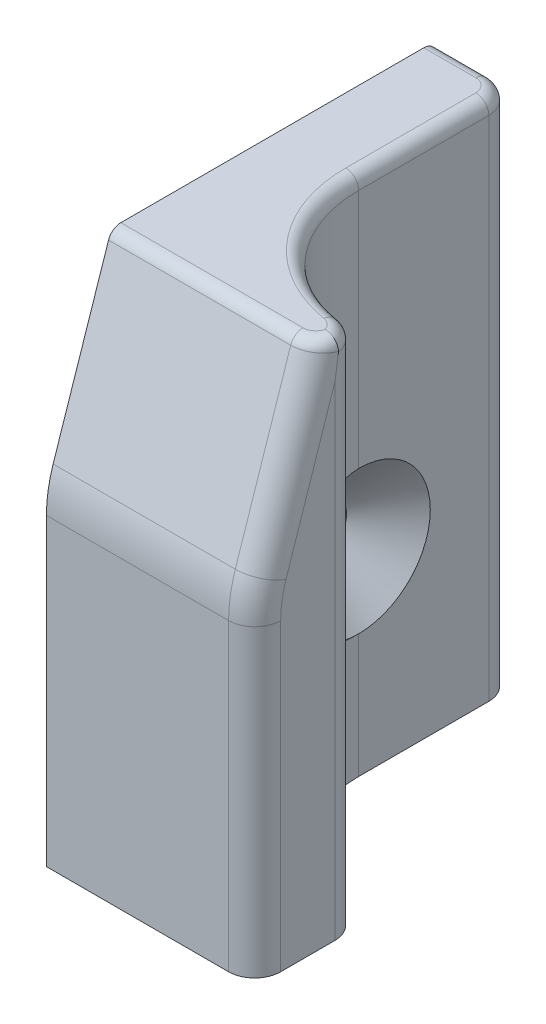
SolidWorks part; units mm, degrees
material "ABS"
ref_plane "Front" through (0, 0, 0) normal (0, 0, 1) x (1, 0, 0)
ref_plane "Top" through (0, 0, 0) normal (0, 1, 0) x (1, 0, 0)
ref_plane "Right" through (0, 0, 0) normal (1, 0, 0) x (0, 0, -1)
sketch "Esquisse1" plane through (0, 0, 0) normal (0, 1, 0) x (1, 0, 0)
  line L0 (-3, 0) -> (3, 0)
  line L1 (3, 0) -> (3, -22)
  line L2 (3, -22) -> (13, -22)
  line L3 (13, -22) -> (13, -30)
  line L4 (13, -30) -> (-3, -30)
  line L7 (-3, -30) -> (-3, 0)
  dimension "D2" = 6
  dimension "D4" = 8
  dimension "D5" = 22
  dimension "D6" = 10
extrude "Boss.-Extru.1" add sketch "Esquisse1" along normal blind 25 and the other way blind 15 from offset 0
chamfer "Chanfrein1" distance 15 distance2 5 1 edges at (5, 25, 30) first distance on face at (5, 5, 30)
fillet "Congé1" radius 10 2 edges at (5, 10, 30) (3, 5, 22)
fillet "Congé2" radius 2 5 edges at (13, -3.3114, 30) (13, 18.2698, 27.2434) (13, 9.979, 29.8709) (3, 5, 0) (13, 5, 22)
fillet "Congé3" radius 1 7 edges at (12.2419, 25, 24.5444) (5.3624, 25, 18.455) (-1, 25, 0) (2.4142, 25, 0.5858) (4, 25, 25) (3, 25, 7) (12.3686, 25, 22.3738)
sketch "Esquisse2" plane through (0, 0, 0) normal (0, 1, 0) x (1, 0, 0)
  line L0 (-3, -1) -> (-3, -24.2792) construction
  line L1 (-3, -12) -> (8.5, -12)
  line L2 (-3, -12) -> (-3, -14)
  line L6 (8.5, -12) -> (14, -12) construction
  line L9 (-3, -14) -> (0.0632, -14)
  line L10 (3, -17.5) -> (0.0632, -14)
  line L13 (3, -17.5) -> (8.5, -17.5)
  line L14 (8.5, -17.5) -> (8.5, -12)
  line L16 (3, -12) -> (3, -2) construction
  line L17 (1, 0) -> (-3, 0) construction
  dimension "D1" = 4
  dimension "D2" = 11
  dimension "D3" = 3.0632
  dimension "D4" = 50
  dimension "D5" = 12
revolve "Enlèvement de matière-Révolution1" cut sketch "Esquisse2" angle 360 about L6
